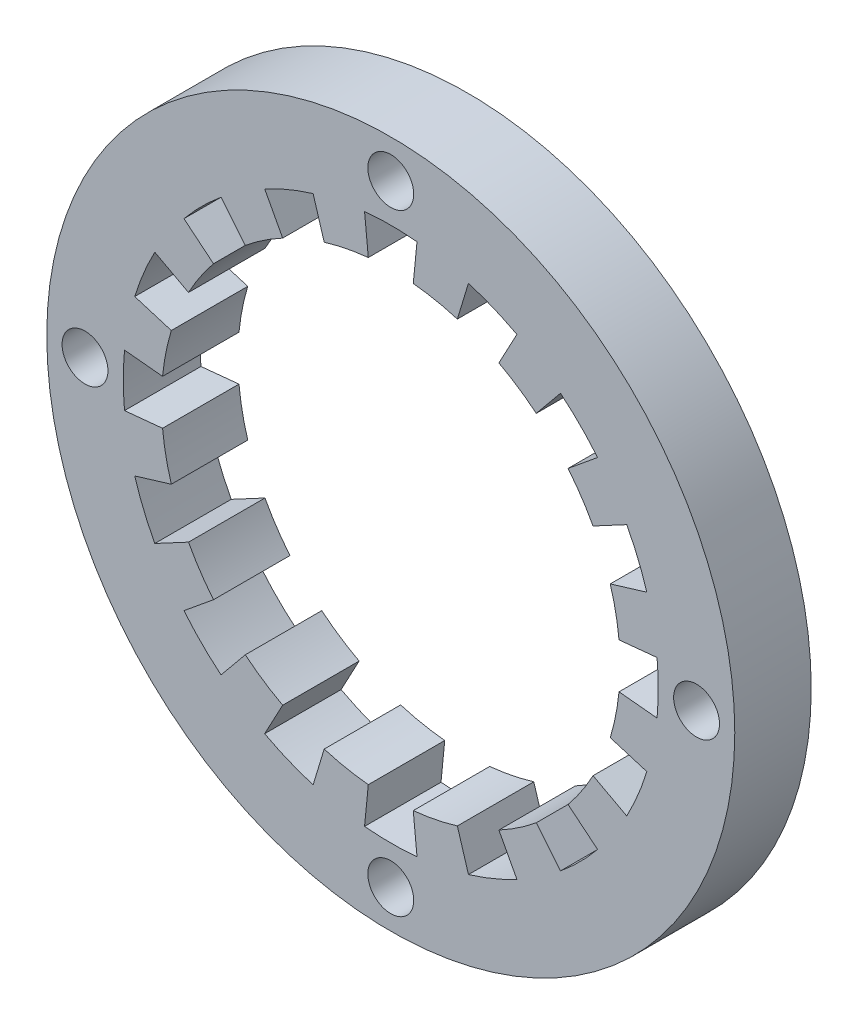
SolidWorks part; units mm, degrees
ref_plane "前视基准面" through (0, 0, 0) normal (0, 0, 1) x (1, 0, 0)
ref_plane "上视基准面" through (0, 0, 0) normal (0, 1, 0) x (1, 0, 0)
ref_plane "右视基准面" through (0, 0, 0) normal (1, 0, 0) x (0, 0, -1)
sketch "草图1" plane through (0, 0, 0) normal (0, 0, 1) x (1, 0, 0)
  line L0 (29.8555, 2.9405) -> (34.8315, 3.4306)
  line L1 (28.7082, 8.7085) -> (33.4929, 10.16)
  line L3 (26.4576, 14.1419) -> (30.8672, 16.4989) [skipped]
  line L4 (28.7082, -8.7085) -> (33.4929, -10.16)
  line L5 (29.8555, -2.9405) -> (34.8315, -3.4306)
  line L6 (23.1903, -19.0318) -> (27.0554, -22.2038)
  line L7 (26.4576, -14.1419) -> (30.8672, -16.4989)
  line L8 (14.1419, -26.4576) -> (16.4989, -30.8672)
  line L9 (19.0318, -23.1903) -> (22.2038, -27.0554)
  line L10 (2.9405, -29.8555) -> (3.4306, -34.8315)
  line L11 (8.7085, -28.7082) -> (10.16, -33.4929)
  line L12 (-8.7085, -28.7082) -> (-10.16, -33.4929)
  line L13 (-2.9405, -29.8555) -> (-3.4306, -34.8315)
  line L14 (-19.0318, -23.1903) -> (-22.2038, -27.0554)
  line L15 (-14.1419, -26.4576) -> (-16.4989, -30.8672)
  line L16 (-26.4576, -14.1419) -> (-30.8672, -16.4989)
  line L17 (-23.1903, -19.0318) -> (-27.0554, -22.2038)
  line L18 (-29.8555, -2.9405) -> (-34.8315, -3.4306)
  line L19 (-28.7082, -8.7085) -> (-33.4929, -10.16)
  line L20 (-28.7082, 8.7085) -> (-33.4929, 10.16)
  line L21 (-29.8555, 2.9405) -> (-34.8315, 3.4306)
  line L22 (-23.1903, 19.0318) -> (-27.0554, 22.2038)
  line L23 (-26.4576, 14.1419) -> (-30.8672, 16.4989)
  line L24 (-14.1419, 26.4576) -> (-16.4989, 30.8672)
  line L25 (-19.0318, 23.1903) -> (-22.2038, 27.0554)
  line L26 (-2.9405, 29.8555) -> (-3.4306, 34.8315)
  line L27 (-8.7085, 28.7082) -> (-10.16, 33.4929)
  line L28 (8.7085, 28.7082) -> (10.16, 33.4929)
  line L29 (2.9405, 29.8555) -> (3.4306, 34.8315)
  line L30 (19.0318, 23.1903) -> (22.2038, 27.0554)
  line L31 (14.1419, 26.4576) -> (16.4989, 30.8672)
  line L32 (26.4576, 14.1419) -> (30.8672, 16.4989)
  line L33 (23.1903, 19.0318) -> (27.0554, 22.2038)
  arc A0 (29.8555, 2.9405) -> (28.7082, 8.7085) centre (0, 0) ccw
  arc A1 (33.4929, 10.16) -> (30.8672, 16.4989) centre (0, 0) ccw
  circle A2 centre (0, 0) radius 45
  arc A3 (28.7082, -8.7085) -> (29.8555, -2.9405) centre (0, 0) ccw
  arc A4 (34.8315, -3.4306) -> (34.8315, 3.4306) centre (0, 0) ccw
  arc A5 (23.1903, -19.0318) -> (26.4576, -14.1419) centre (0, 0) ccw
  arc A6 (30.8672, -16.4989) -> (33.4929, -10.16) centre (0, 0) ccw
  arc A7 (14.1419, -26.4576) -> (19.0318, -23.1903) centre (0, 0) ccw
  arc A8 (22.2038, -27.0554) -> (27.0554, -22.2038) centre (0, 0) ccw
  arc A9 (2.9405, -29.8555) -> (8.7085, -28.7082) centre (0, 0) ccw
  arc A10 (10.16, -33.4929) -> (16.4989, -30.8672) centre (0, 0) ccw
  arc A11 (-8.7085, -28.7082) -> (-2.9405, -29.8555) centre (0, 0) ccw
  arc A12 (-3.4306, -34.8315) -> (3.4306, -34.8315) centre (0, 0) ccw
  arc A13 (-19.0318, -23.1903) -> (-14.1419, -26.4576) centre (0, 0) ccw
  arc A14 (-16.4989, -30.8672) -> (-10.16, -33.4929) centre (0, 0) ccw
  arc A15 (-26.4576, -14.1419) -> (-23.1903, -19.0318) centre (0, 0) ccw
  arc A16 (-27.0554, -22.2038) -> (-22.2038, -27.0554) centre (0, 0) ccw
  arc A17 (-29.8555, -2.9405) -> (-28.7082, -8.7085) centre (0, 0) ccw
  arc A18 (-33.4929, -10.16) -> (-30.8672, -16.4989) centre (0, 0) ccw
  arc A19 (-28.7082, 8.7085) -> (-29.8555, 2.9405) centre (0, 0) ccw
  arc A20 (-34.8315, 3.4306) -> (-34.8315, -3.4306) centre (0, 0) ccw
  arc A21 (-23.1903, 19.0318) -> (-26.4576, 14.1419) centre (0, 0) ccw
  arc A22 (-30.8672, 16.4989) -> (-33.4929, 10.16) centre (0, 0) ccw
  arc A23 (-14.1419, 26.4576) -> (-19.0318, 23.1903) centre (0, 0) ccw
  arc A24 (-22.2038, 27.0554) -> (-27.0554, 22.2038) centre (0, 0) ccw
  arc A25 (-2.9405, 29.8555) -> (-8.7085, 28.7082) centre (0, 0) ccw
  arc A26 (-10.16, 33.4929) -> (-16.4989, 30.8672) centre (0, 0) ccw
  arc A27 (8.7085, 28.7082) -> (2.9405, 29.8555) centre (0, 0) ccw
  arc A28 (3.4306, 34.8315) -> (-3.4306, 34.8315) centre (0, 0) ccw
  arc A29 (19.0318, 23.1903) -> (14.1419, 26.4576) centre (0, 0) ccw
  arc A30 (16.4989, 30.8672) -> (10.16, 33.4929) centre (0, 0) ccw
  arc A31 (26.4576, 14.1419) -> (23.1903, 19.0318) centre (0, 0) ccw
  arc A32 (27.0554, 22.2038) -> (22.2038, 27.0554) centre (0, 0) ccw
  point P10 (0, 0)
  point P89 (0, 0)
  dimension "D1" = 3
  dimension "D2" = 16
extrude "凸台-拉伸1" add sketch "草图1" along normal blind 5 and the other way blind 5
sketch "草图2" plane through (0, 0, 0) normal (0, 0, 1) x (1, 0, 0)
  circle A1 centre (40, 0) radius 3
  circle A3 centre (0, -40) radius 3
  circle A5 centre (-40, 0) radius 3
  circle A7 centre (0, 40) radius 3
  circle A9 centre (-28.2843, -28.2843) radius 3 [skipped]
  circle A10 centre (28.2843, 28.2843) radius 3 [skipped]
  circle A11 centre (-28.2843, 28.2843) radius 3 [skipped]
  circle A12 centre (28.2843, -28.2843) radius 3 [skipped]
  point P19 (0, 0)
  dimension "D1" = 8
extrude "切除-拉伸1" cut sketch "草图2" along normal through all and the other way through all
